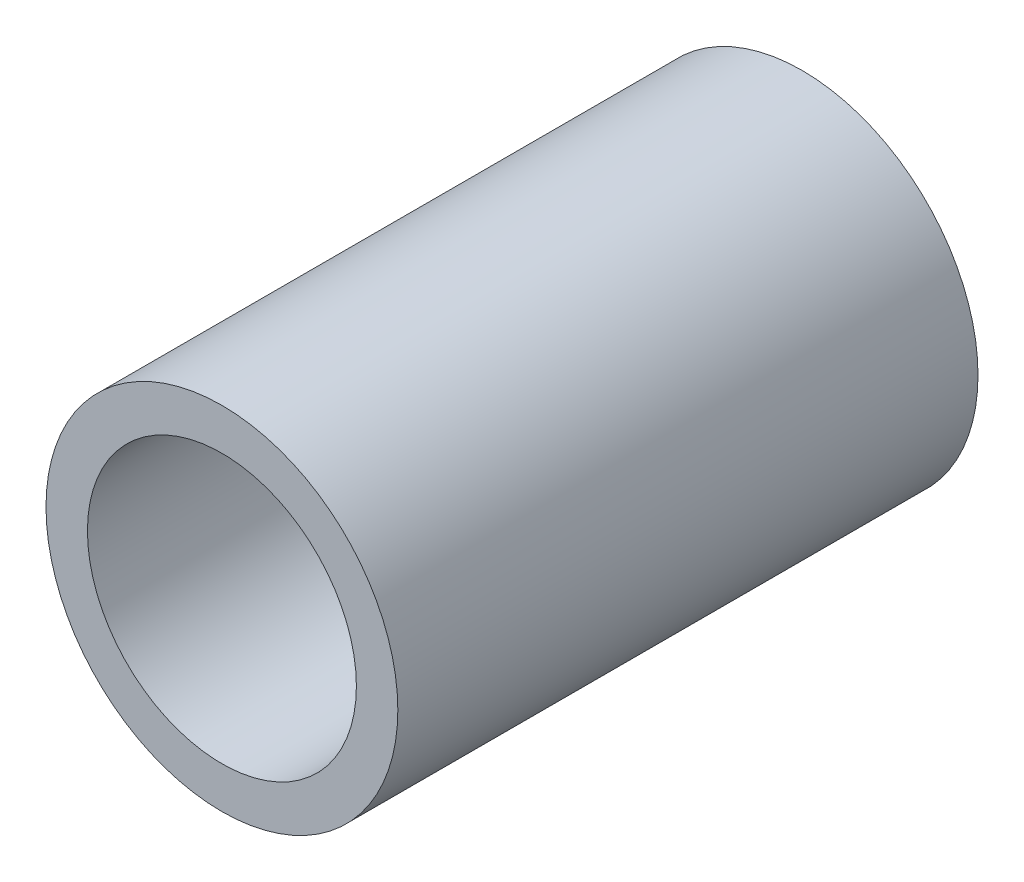
SolidWorks part; units mm, degrees
ref_plane "Front Plane" through (0, 0, 0) normal (0, 0, 1) x (1, 0, 0)
ref_plane "Top Plane" through (0, 0, 0) normal (0, 1, 0) x (1, 0, 0)
ref_plane "Right Plane" through (0, 0, 0) normal (1, 0, 0) x (0, 0, -1)
sketch "Sketch1" plane through (0, 0, 0) normal (0, 0, 1) x (1, 0, 0)
  circle A0 centre (0, 0) radius 4.245
  circle A1 centre (0, 0) radius 3.245
  dimension "D1" = 6.49
  dimension "D2" = 8.49
extrude "Boss-Extrude1" add sketch "Sketch1" along normal blind 14
thread "Thread1" pitch 1 method cut profile "Thread Profile1" start angle 0, offset 0, length 4, pitch 1, diameter 6.49
ref_plane "Plane1" through (3.245, 0, 0) normal (0, -1, 0) x (1, 0, 0)
sketch "Thread Profile1" plane through (3.245, 0, 0) normal (0, -1, 0) x (1, 0, 0)
  line L0 (0, 0) -> (0, 1) construction
  line L1 (0, 0) -> (0.5413, 0.3125)
  line L2 (0.5413, 0.3125) -> (0.5413, 0.4375)
  line L3 (0.5413, 0.4375) -> (0, 0.75)
  line L4 (0.5413, 0.375) -> (0, 0.375) construction
  line L11 (0, 0) -> (0, 0.75)
  point P2 (0, 0)
  dimension "Pitch" = 1
  dimension "Profile_Angle" = 60
  dimension "Profile_Land" = 0.125
  dimension "Profile_Height" = 0.5413
